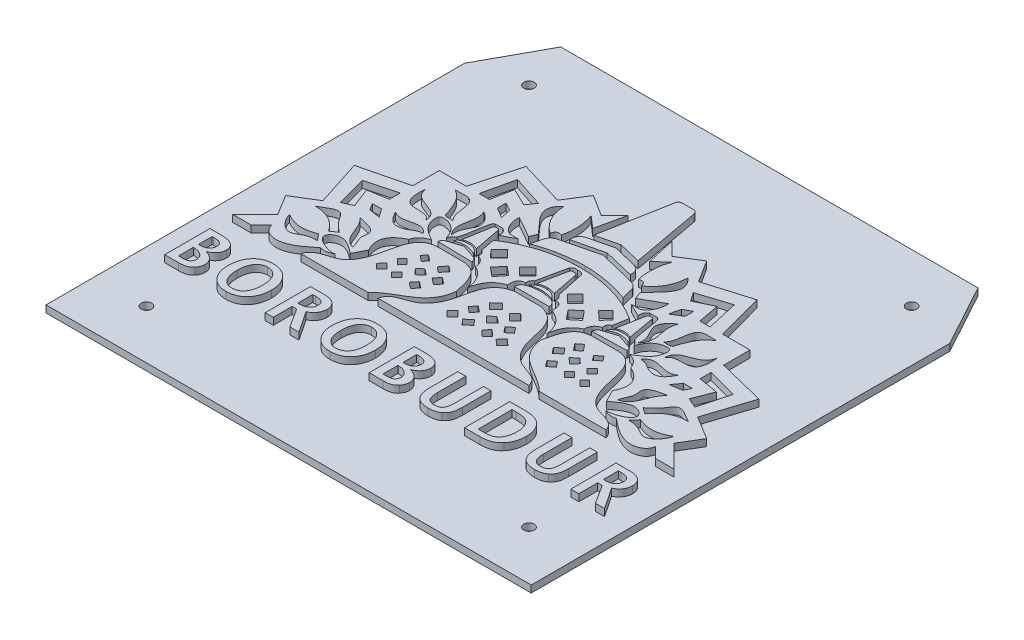
SolidWorks part; units mm, degrees
ref_plane "Front Plane" through (0, 0, 0) normal (0, 0, 1) x (1, 0, 0)
ref_plane "Top Plane" through (0, 0, 0) normal (0, 1, 0) x (1, 0, 0)
ref_plane "Right Plane" through (0, 0, 0) normal (1, 0, 0) x (0, 0, -1)
sketch "Sketch2" plane through (0, 0, 0) normal (0, 1, 0) x (1, 0, 0)
  line L0 (-69.75, 120.33) -> (-69.75, 0)
  line L1 (-69.75, 0) -> (69.75, 0)
  line L2 (69.75, 0) -> (69.75, 120.33)
  line L3 (69.75, 120.33) -> (59.98, 138.2123)
  line L4 (59.98, 138.2123) -> (-59.98, 138.2123)
  line L5 (-59.98, 138.2123) -> (-69.75, 120.33)
  line L6 (-55, 124.11) -> (-55, 14.11) construction
  line L7 (-55, 14.11) -> (55, 14.11) construction
  line L8 (55, 14.11) -> (55, 124.11) construction
  line L9 (55, 124.11) -> (-55, 124.11) construction
  line L10 (0, 14.11) -> (0, 0) construction
  circle A0 centre (-55, 124.11) radius 1.5
  circle A1 centre (55, 124.11) radius 1.5
  circle A2 centre (55, 14.11) radius 1.5
  circle A3 centre (-55, 14.11) radius 1.5
  point P6 (0, 0)
  dimension "D6" = 3
  dimension "D1" = 139.5
  dimension "D2" = 120.33
  dimension "D3" = 118.65
  dimension "D4" = 118.65
  dimension "D5" = 119.96
  dimension "D7" = 110
  dimension "D8" = 110
  dimension "D9" = 14.11
extrude "Boss-Extrude1" add sketch "Sketch2" along normal blind 2
sketch "Sketch5" plane through (0, 2, 0) normal (0, 1, 0) x (1, 0, 0)
  line L0 (-492.273, -111.0065) -> (-56.9397, -111.0065) construction
  line L3 (0, 0) -> (0, 138.2123) construction
  line L4 (59.98, 138.2123) -> (-59.98, 138.2123) construction
  line L5 (-499.4365, -25.4656) -> (-64.1032, -25.4656) construction
  line L6 (0, 47.3754) -> (-21.6859, 47.3754)
  line L7 (-24.6018, 47.3754) -> (-43.8626, 47.3754)
  line L8 (-25.7541, 68.7243) -> (-18.7302, 68.7243)
  line L9 (-22.2422, 68.7243) -> (-22.2422, 47.3754) construction
  line L10 (-3.7057, 68.7243) -> (0, 68.7243)
  line L11 (-19.5144, 78.4449) -> (-18.7302, 74.224)
  line L12 (-1.7255, 82.4366) -> (-3.4837, 74.224)
  line L13 (-1.013, 81.2435) -> (-2.4679, 73.9099)
  line L14 (0, 91.6011) -> (-8.7196, 89.5051)
  line L15 (0, 95.6184) -> (-6.3568, 94.0901)
  line L16 (-6.3568, 94.0901) -> (-2.7736, 113.7579)
  line L17 (-1.4606, 114.8023) -> (0, 114.8023)
  line L18 (0, 90.4895) -> (-10.1933, 87.9731)
  line L19 (-12.4793, 86.3667) -> (-13.4352, 82.7244)
  line L20 (-6.3568, 103.9184) -> (-10.1933, 100.082)
  line L21 (-10.1933, 100.082) -> (-16.2824, 103.9184)
  line L22 (-16.2824, 103.9184) -> (-20.2698, 97.5897)
  line L23 (-20.2698, 97.5897) -> (-33.217, 101.4709)
  line L24 (-33.217, 101.4709) -> (-36.8387, 87.9731)
  line L25 (-36.8387, 87.9731) -> (-44.6751, 87.9731)
  line L26 (-44.6751, 87.9731) -> (-44.6751, 80.3944)
  line L27 (-44.6751, 80.3944) -> (-58.1708, 77.0507)
  line L28 (-58.1708, 77.0507) -> (-53.8631, 63.7358)
  line L29 (-53.8631, 63.7358) -> (-60.5227, 59.6742)
  line L30 (-60.5227, 59.6742) -> (-56.9815, 53.8678)
  line L31 (-56.9815, 53.8678) -> (-63.4739, 47.3754)
  line L32 (-63.4739, 47.3754) -> (-58.1708, 47.3754)
  line L33 (-58.1708, 47.3754) -> (-55.1522, 50.3941)
  line L34 (-46.3062, 54.8983) -> (-44.6751, 52.9547)
  line L35 (-6.3568, 103.9184) -> (-8.1937, 95.6184)
  line L36 (-8.1937, 95.6184) -> (-11.6081, 98.5775)
  line L37 (-30.2456, 87.9731) -> (-29.1015, 94.0901)
  line L38 (-29.1015, 94.0901) -> (-23.9639, 91.6011)
  line L39 (-23.9639, 91.6011) -> (-22.2422, 94.0901)
  line L40 (-22.2422, 94.0901) -> (-31.1681, 96.9522)
  line L41 (-31.1681, 96.9522) -> (-33.217, 87.9731)
  line L42 (-33.217, 87.9731) -> (-30.2456, 87.9731)
  line L43 (-46.0099, 70.1281) -> (-44.9506, 68.2469)
  line L44 (-44.9506, 68.2469) -> (-41.688, 67.7366)
  line L45 (-41.688, 67.7366) -> (-43.4326, 70.1281)
  line L46 (-43.4326, 70.1281) -> (-46.0099, 70.1281)
  line L47 (-50.9674, 65.8317) -> (-48.0862, 67.0605)
  line L48 (-48.0862, 67.0605) -> (-50.2895, 72.681)
  line L49 (-50.2895, 72.681) -> (-44.6751, 73.6456)
  line L50 (-44.6751, 73.6456) -> (-44.6751, 76.7636)
  line L51 (-44.6751, 76.7636) -> (-53.3034, 74.4572)
  line L52 (-53.3034, 74.4572) -> (-50.9674, 65.8317)
  line L53 (-36.8387, 54.5399) -> (-35.0144, 58.0517)
  line L54 (-45.4914, 56.9812) -> (-43.6659, 58.2376)
  line L55 (-22.2422, 72.681) -> (-26.2797, 71.3942)
  line L56 (-27.1911, 70.1281) -> (-17.17, 69.9143)
  line L57 (-22.2422, 72.681) -> (-17.8234, 71.2032)
  line L58 (-26.9657, 89.4844) -> (-26.9657, 87.0105)
  line L59 (-26.9657, 87.0105) -> (-23.9639, 85.1856)
  line L60 (-23.9639, 85.1856) -> (-24.7105, 88.2474)
  line L61 (-24.7105, 88.2474) -> (-26.9657, 89.4844)
  line L62 (0, 56.8345) -> (-1.7255, 58.5599)
  line L63 (-1.7255, 58.5599) -> (0, 59.9061)
  line L64 (-4.57, 62.2541) -> (-2.898, 60.5821)
  line L65 (-2.898, 60.5821) -> (-1.013, 62.4672)
  line L66 (-1.013, 62.4672) -> (-2.6352, 64.0895)
  line L67 (-2.6352, 64.0895) -> (-4.57, 62.2541)
  line L68 (-6.6579, 58.2482) -> (-4.9516, 56.908)
  line L69 (-6.6579, 58.2482) -> (-5.3758, 59.8806)
  line L70 (-4.9516, 56.908) -> (-3.6695, 58.5404)
  line L71 (-5.3758, 59.8806) -> (-3.6695, 58.5404)
  line L72 (-4.3197, 54.3049) -> (-2.898, 52.7842)
  line L73 (-4.3197, 54.3049) -> (-2.5487, 55.9606)
  line L74 (-2.898, 52.7842) -> (-1.127, 54.4399)
  line L75 (-2.5487, 55.9606) -> (-1.127, 54.4399)
  line L76 (-8.7196, 54.3049) -> (-7.1489, 52.6248)
  line L77 (-8.7196, 54.3049) -> (-7.0939, 55.8247)
  line L78 (-7.1489, 52.6248) -> (-5.5232, 54.1446)
  line L79 (-7.0939, 55.8247) -> (-5.5232, 54.1446)
  line L80 (-21.1518, 55.8377) -> (-19.4037, 54.4647)
  line L81 (-21.1518, 55.8377) -> (-19.8599, 57.4825)
  line L82 (-19.4037, 54.4647) -> (-18.1117, 56.1095)
  line L83 (-19.8599, 57.4825) -> (-18.1117, 56.1095)
  line L84 (-18.9101, 60.1733) -> (-17.0591, 58.7194)
  line L85 (-18.9101, 60.1733) -> (-17.6103, 61.8282)
  line L86 (-17.0591, 58.7194) -> (-15.7593, 60.3743)
  line L87 (-17.6103, 61.8282) -> (-15.7593, 60.3743)
  line L88 (-20.9944, 63.7167) -> (-19.4037, 62.4672)
  line L89 (-20.9944, 63.7167) -> (-19.5144, 65.6009)
  line L90 (-19.4037, 62.4672) -> (-17.9236, 64.3515)
  line L91 (-19.5144, 65.6009) -> (-17.9236, 64.3515)
  line L92 (-26.2797, 64.0895) -> (-24.6018, 62.7715)
  line L93 (-26.2797, 64.0895) -> (-25.2216, 65.4366)
  line L94 (-24.6018, 62.7715) -> (-23.5437, 64.1187)
  line L95 (-25.2216, 65.4366) -> (-23.5437, 64.1187)
  line L96 (-22.2422, 61.464) -> (-23.7093, 60.1733)
  line L97 (-23.7093, 60.1733) -> (-22.2422, 58.5404)
  line L98 (-22.2422, 58.5404) -> (-20.5282, 60.0802)
  line L99 (-20.5282, 60.0802) -> (-22.2422, 61.464)
  line L100 (-28.7512, 60.0802) -> (-27.1911, 58.5404)
  line L101 (-28.7512, 60.0802) -> (-27.4069, 61.4423)
  line L102 (-27.1911, 58.5404) -> (-25.8467, 59.9024)
  line L103 (-27.4069, 61.4423) -> (-25.8467, 59.9024)
  line L104 (-26.2797, 55.8377) -> (-24.8885, 54.4647)
  line L105 (-26.2797, 55.8377) -> (-24.7708, 57.3665)
  line L106 (-24.8885, 54.4647) -> (-23.3797, 55.9934)
  line L107 (-24.7708, 57.3665) -> (-23.3797, 55.9934)
  line L108 (-30.6365, 55.8377) -> (-29.2453, 54.4647)
  line L109 (-30.6365, 55.8377) -> (-29.0938, 57.4008)
  line L110 (-29.2453, 54.4647) -> (-27.7026, 56.0277)
  line L111 (-29.0938, 57.4008) -> (-27.7026, 56.0277)
  line L112 (-17.5779, 75.7199) -> (-15.5694, 73.6456)
  line L113 (-17.5779, 75.7199) -> (-15.1083, 78.1111)
  line L114 (-15.5694, 73.6456) -> (-13.0998, 76.0368)
  line L115 (-15.1083, 78.1111) -> (-13.0998, 76.0368)
  line L116 (-13.2677, 71.2568) -> (-10.6976, 69.1502)
  line L117 (-13.2677, 71.2568) -> (-11.093, 73.9099)
  line L118 (-10.6976, 69.1502) -> (-8.5229, 71.8032)
  line L119 (-11.093, 73.9099) -> (-8.5229, 71.8032)
  line L120 (-9.1064, 75.5043) -> (-6.9213, 73.2802)
  line L121 (-9.1064, 75.5043) -> (-6.6904, 77.8778)
  line L122 (-6.9213, 73.2802) -> (-4.5053, 75.6536)
  line L123 (-6.6904, 77.8778) -> (-4.5053, 75.6536)
  line L124 (-23.3797, 82.7244) -> (-21.1518, 82.7244)
  line L125 (-16.2824, 82.29) -> (-20.0337, 80.3944)
  line L126 (-21.4739, 87.796) -> (-15.3829, 84.3725)
  line L127 (-15.3829, 84.3725) -> (-14.6072, 86.3667)
  line L128 (-18.7302, 82.29) -> (-16.2824, 82.29)
  line L129 (0, 114.8023) -> (0, 95.6184)
  line L130 (0, 91.6011) -> (0, 94.0901)
  line L131 (0, 94.0901) -> (-6.9213, 92.4263)
  line L132 (0, 90.4895) -> (0, 85.1856)
  line L133 (0, 84.0727) -> (0, 83.0699)
  line L134 (0, 82.0012) -> (0, 74.4572)
  line L135 (0, 73.9099) -> (0, 72.8637)
  line L136 (0, 72.5184) -> (0, 69.9143)
  line L137 (0, 68.7243) -> (0, 47.3754)
  line L138 (-24.2404, 73.9099) -> (-22.9425, 81.459)
  line L139 (-19.8599, 73.8153) -> (-21.3384, 81.459)
  spline S0 degree 3 poles (-43.8626, 47.3754) (-42.9521, 50.5844) (-36.4958, 50.0974) (-31.3645, 59.4416) (-31.9209, 68.6588) (-25.7541, 68.7243) knots 0 0 0 0 0.285538 0.498981 1 1 1 1
  spline S1 degree 3 poles (-12.1467, 60.4138) (-13.0855, 64.6613) (-13.8787, 68.6728) (-18.7302, 68.7243) knots 0.60584 0.60584 0.60584 0.60584 1 1 1 1
  spline S2 degree 3 poles (-24.6018, 47.3754) (-20.4059, 51.9406) (-12.8785, 52.3753) (-12.1467, 60.4138) knots 0 0 0 0 1 1 1 1
  spline S3 degree 3 poles (-21.6859, 47.3754) (-21.0603, 50.4734) (-15.3356, 50.4348) (-8.8142, 58.6677) (-10.5494, 67.4068) (-3.7057, 68.7243) knots 0 0 0 0 0.270547 0.473964 1 1 1 1
  spline S4 degree 2 poles (0, 84.0727) (-10.6051, 84.197) (-19.5144, 78.4449) knots 0 0 0 1 1 1
  spline S5 degree 2 poles (-18.7302, 74.224) (-17.5047, 73.6029) (-17.8234, 72.3602) knots 0 0 0 1 1 1
  spline S6 degree 2 poles (-17.8234, 72.3602) (-15.651, 71.6726) (-15.5694, 69.3242) knots 0 0 0 1 1 1
  spline S7 degree 2 poles (-15.5694, 69.3242) (-11.7671, 67.3735) (-11.4229, 62.8919) knots 0 0 0 1 1 1
  spline S8 degree 2 poles (-11.4229, 62.8919) (-10.8067, 67.7648) (-6.3568, 69.3242) knots 0 0 0 1 1 1
  spline S9 degree 2 poles (-4.3084, 72.3602) (-6.6845, 72.4435) (-6.3568, 69.3242) knots 0 0 0 1 1 1
  spline S10 degree 2 poles (-4.3084, 72.3602) (-4.4719, 73.5979) (-3.4837, 74.224) knots 0 0 0 1 1 1
  spline S11 degree 2 poles (0, 83.0699) (-1.1111, 83.4064) (-1.7255, 82.4366) knots 0 0 0 1 1 1
  spline S12 degree 3 poles (0, 82.0012) (-0.5463, 82.1465) (-0.8839, 81.8939) (-1.013, 81.2435) knots 0 0 0 0 1 1 1 1
  spline S13 degree 2 poles (0, 74.4572) (-1.2543, 74.2752) (-2.4679, 73.9099) knots 0 0 0 1 1 1
  spline S14 degree 2 poles (0, 73.9099) (-2.061, 73.9775) (-3.2599, 72.3602) knots 0 0 0 1 1 1
  spline S15 degree 2 poles (-3.2599, 72.3602) (-1.6557, 72.7761) (0, 72.8637) knots 0 0 0 1 1 1
  spline S16 degree 3 poles (0, 72.5184) (-1.8552, 72.1989) (-4.9711, 72.3963) (-4.9908, 69.9143) knots 0 0 0 0 1 1 1 1
  spline S17 degree 1 poles (0, 69.9143) (-4.9908, 69.9143) knots 0 0 1 1
  spline S18 degree 2 poles (-2.7736, 113.7579) (-2.545, 114.8416) (-1.4606, 114.8023) knots 0 0 0 1 1 1
  spline S19 degree 2 poles (-10.1933, 87.9731) (-11.7123, 87.6861) (-12.4793, 86.3667) knots 0 0 0 1 1 1
  spline S20 degree 2 poles (-13.4352, 82.7244) (-6.9507, 85.146) (0, 85.1856) knots 0 0 0 1 1 1
  spline S21 degree 3 poles (-55.1522, 50.3941) (-54.8966, 48.4539) (-49.6723, 45.6985) (-44.8611, 49.7991) (-42.5456, 51.7133) knots 0 0 0 0 0.336939 1 1 1 1
  spline S22 degree 2 poles (-55.1522, 55.4537) (-50.8462, 52.8644) (-46.3062, 54.8983) knots 0 0 0 1 1 1
  spline S23 degree 3 poles (-55.1522, 55.4537) (-55.0749, 53.8847) (-52.1611, 50.1271) (-48.2771, 52.3365) (-46.3808, 53.264) (-44.6751, 52.9547) knots 0 0 0 0 0.513802 0.617376 1 1 1 1
  spline S24 degree 2 poles (-11.6081, 98.5775) (-9.9467, 94.1512) (-11.093, 89.5051) knots 0 0 0 1 1 1
  spline S25 degree 2 poles (-17.8234, 96.9522) (-17.5779, 91.4078) (-13.1084, 88.2984) knots 0 0 0 1 1 1
  spline S26 degree 2 poles (-11.093, 89.5051) (-12.8256, 90.0868) (-13.1084, 88.2984) knots 0 0 0 1 1 1
  spline S27 degree 3 poles (-17.8234, 96.9522) (-22.4568, 92.8593) (-16.859, 89.4672) (-14.6072, 86.3667) knots 0 0 0 0 1 1 1 1
  spline S28 degree 3 poles (-38.9362, 52.2621) (-40.0045, 51.7087) (-47.0477, 54.0125) (-41.8461, 58.7473) (-38.3314, 55.7308) (-36.8387, 54.5399) knots 0 0 0 0 0.430134 0.559823 1 1 1 1
  spline S29 degree 2 poles (-42.5456, 51.7133) (-40.661, 51.1729) (-38.9362, 52.2621) knots 0 0 0 1 1 1
  spline S30 degree 2 poles (-35.0144, 58.0517) (-38.0223, 63.5186) (-31.9435, 66.4334) knots 0 0 0 1 1 1
  spline S31 degree 2 poles (-31.9435, 66.4334) (-31.0893, 68.9745) (-28.4778, 69.5574) knots 0 0 0 1 1 1
  spline S32 degree 3 poles (-53.6634, 61.3327) (-52.0615, 61.3174) (-48.9555, 60.6674) (-46.5857, 58.5712) (-45.4914, 56.9812) knots 0.005198 0.005198 0.005198 0.005198 0.462661 1 1 1 1
  spline S33 degree 3 poles (-53.6634, 61.3327) (-53.1598, 61.3764) (-51.0222, 63.1399) (-48.1912, 63.6957) (-46.5269, 60.5729) (-45.0294, 59.3254) (-43.6659, 58.2376) knots 0.01154 0.01154 0.01154 0.01154 0.305761 0.43615 0.629288 0.980308 0.980308 0.980308 0.980308
  spline S34 degree 3 poles (-44.3415, 64.8566) (-41.415, 62.5208) (-42.1713, 57.6443) (-38.0292, 56.4621) knots 0 0 0 0 1 1 1 1
  spline S35 degree 3 poles (-44.3415, 64.8566) (-43.3621, 64.5853) (-38.4355, 64.1691) (-39.7393, 59.4545) (-38.5212, 58.5122) (-38.0292, 56.4621) knots 0 0 0 0 0.474827 0.654779 1 1 1 1
  spline S36 degree 2 poles (-26.2797, 71.3942) (-27.1006, 71.0073) (-27.1911, 70.1281) knots 0 0 0 1 1 1
  spline S37 degree 2 poles (-17.17, 69.9143) (-17.41, 70.6055) (-17.8234, 71.2032) knots 0 0 0 1 1 1
  spline S38 degree 3 poles (-28.4778, 69.5574) (-30.532, 70.8025) (-33.2273, 72.1143) (-33.496, 76.7183) (-29.6669, 76.9172) (-27.6003, 74.7511) (-26.9657, 72.3602) knots 0 0 0 0 0.406747 0.533053 0.591311 1 1 1 1
  spline S39 degree 3 poles (-40.6457, 71.3942) (-40.149, 70.4981) (-38.7583, 67.6743) (-34.408, 68.2779) (-32.8852, 70.1036) (-31.2827, 69.9143) knots 0 0 0 0 0.360983 0.637936 1 1 1 1
  spline S40 degree 3 poles (-40.6457, 71.3942) (-37.5907, 68.9893) (-33.7089, 73.6061) (-31.2827, 69.9143) knots 0 0 0 0 1 1 1 1
  spline S41 degree 3 poles (-41.9555, 81.2435) (-42.2243, 79.8321) (-42.3033, 73.0878) (-35.3191, 76.123) (-34.2379, 73.6456) knots 0 0 0 0 0.454885 1 1 1 1
  spline S42 degree 3 poles (-41.9555, 81.2435) (-41.3021, 76.4362) (-34.3542, 78.6828) (-34.2379, 73.6456) knots 0 0 0 0 1 1 1 1
  spline S43 degree 3 poles (-37.6021, 85.5111) (-36.2893, 85.3647) (-32.5423, 86.252) (-31.55, 81.2084) (-31.5002, 78.8462) (-30.2456, 77.5331) knots 0 0 0 0 0.366527 0.616998 1 1 1 1
  spline S44 degree 3 poles (-37.6021, 85.5111) (-35.3214, 84.0723) (-34.43, 82.5142) (-32.8279, 78.4091) (-32.8292, 77.5539) (-31.8585, 77.4446) (-30.2456, 77.5331) knots 0 0 0 0 0.537998 0.5989 0.784193 1 1 1 1
  spline S45 degree 3 poles (-26.7833, 73.6456) (-29.9664, 76.7264) (-26.2408, 80.5894) (-27.9589, 84.0727) knots 0 0 0 0 1 1 1 1
  spline S46 degree 3 poles (-27.9589, 84.0727) (-26.7849, 83.491) (-24.1776, 81.0218) (-26.3254, 77.2487) (-27.2945, 75.2172) (-26.7833, 73.6456) knots 0 0 0 0 0.40452 0.640919 1 1 1 1
  spline S47 degree 2 poles (-26.9657, 72.3602) (-26.4261, 73.2935) (-25.5469, 73.9099) knots 0 0 0 1 1 1
  spline S48 degree 3 poles (-25.5469, 73.9099) (-24.5336, 77.1889) (-24.6874, 79.2624) (-23.839, 82.4674) (-23.3797, 82.7244) knots 0 0 0 0 0.838059 1 1 1 1
  spline S49 degree 2 poles (-21.1518, 82.7244) (-19.8203, 82.0978) (-20.0337, 80.3944) knots 0 0 0 1 1 1
  spline S50 degree 3 poles (-21.4739, 87.796) (-21.6513, 85.7069) (-20.7412, 83.2153) (-18.7302, 82.29) knots 0 0 0 0 1 1 1 1
  spline S51 degree 2 poles (-6.9213, 92.4263) (-8.9157, 91.7486) (-8.7196, 89.5051) knots 0 0 0 1 1 1
  spline S52 degree 2 poles (-25.0807, 72.5184) (-22.0209, 73.768) (-19.0758, 72.1843) knots 0 0 0 1 1 1
  spline S53 degree 2 poles (-24.2404, 73.9099) (-22.0526, 75.0527) (-19.8599, 73.8153) knots 0 0 0 1 1 1
  spline S54 degree 3 poles (-25.0807, 72.5184) (-24.9657, 73.5121) (-22.2153, 74.2838) (-19.7538, 73.7674) (-19.0758, 72.1843) knots 0 0 0 0 0.375201 1 1 1 1
  spline S55 degree 3 poles (-22.9425, 81.459) (-22.8734, 82.2381) (-21.4069, 82.247) (-21.3384, 81.459) knots 0 0 0 0 1 1 1 1
  point P156 (-53.718, 61.3331)
  point P301 (-22.7495, 81.9258)
  point P303 (-21.5703, 81.8742)
  point P304 (-22.7347, 81.8521)
extrude "Boss-Extrude6" add sketch "Sketch5" along normal blind 2 contours L7 S2 S1 L8 S0 L109 L111 L110 L108 L105 L107 L106 L104 L101 L103 L102 L100 L93 L95 L94 L92 L89 L91 L90 L88 L85 L87 L86 L84 L81 L83 L82 L80 L99 L98 L97 L96 | S3 L6 L137 L62 L63 L10 L67 L66 L65 L64 L69 L71 L70 L68 L73 L75 L74 L72 L77 L79 L78 L76 | S11 L133 S4 L11 S5 S6 S7 S8 S9 S10 L12 L121 L123 L122 L120 L117 L119 L118 L116 L113 L115 L114 L112 | S13 L134 S12 L13 | S14 S15 L135 | S17 L136 S16 | L19 S20 L132 L18 S19 | S18 L16 L15 L129 L17 | L131 S51 L14 L130 | S55 L138 S53 L139 | S54 S52 | L56 S37 L57 L55 S36 | S50 L126 L127 S27 S25 S26 S24 L36 L35 L20 L21 L22 L23 L24 L25 L26 L27 L28 L29 L30 L31 L32 L33 S21 S29 S28 L53 S30 S31 S38 S47 S48 L124 S49 L125 L128 S44 S43 S23 S22 L34 L61 L60 L59 L58 L52 L51 region at (-7.1497, 2, -55.8216) region at (-25.1873, 2, -57.442) region at (-10.1075, 2, -76.1716) region at (-0.8987, 2, -77.4798) region at (-4.2282, 2, -91.8003) region at (-2.3815, 2, -103.4294) region at (-6.1376, 2, -86.6784) region at (-8.0602, 2, -99.9421) region at (-22.1691, 2, -71.0071) region at (-1.3183, 2, -73.1828) region at (-2.2004, 2, -71.0201) region at (-22.0913, 2, -77.4687) region at (-22.1381, 2, -73.2833)
sketch "Sketch4" plane through (0, 2, 0) normal (0, 1, 0) x (1, 0, 0)
  text T0 "BOROBUDUR" font "Lucida Sans Unicode" height 13
  point P1 (-42.6909, 27.0637)
  point P2 (-44.2843, 26.8361)
extrude "Boss-Extrude3" add sketch "Sketch4" along normal blind 2
mirror "Mirror1" about plane through (0, 4, 0) normal (1, 0, 0) of "Boss-Extrude6"
